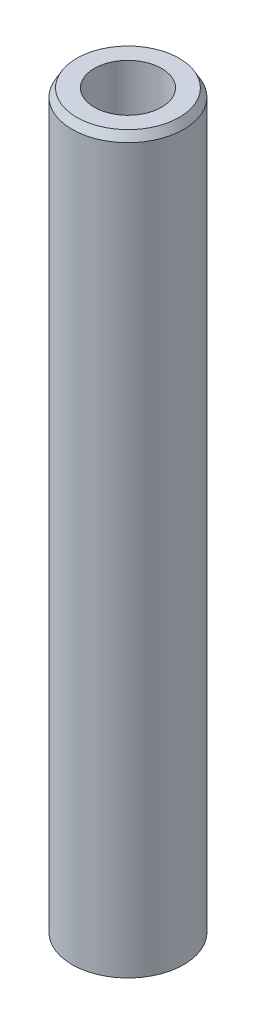
SolidWorks part; units mm, degrees
ref_plane "Front Plane" through (0, 0, 0) normal (0, 0, 1) x (1, 0, 0)
ref_plane "Top Plane" through (0, 0, 0) normal (0, 1, 0) x (1, 0, 0)
ref_plane "Right Plane" through (0, 0, 0) normal (1, 0, 0) x (0, 0, -1)
sketch "Sketch1" plane through (0, 0, 0) normal (0, 1, 0) x (1, 0, 0)
  circle A0 centre (0, 0) radius 30
  dimension "SHAFT_OD" = 60
extrude "Boss-Extrude1" add sketch "Sketch1" along normal blind 395.2318
sketch "Sketch2" plane through (0, 0, 0) normal (0, 1, 0) x (1, 0, 0)
  circle A0 centre (0, 0) radius 18.0728
  dimension "BORE_D" = 36.1455
extrude "Cut-Extrude1" cut sketch "Sketch2" along normal through all
chamfer "Chamfer1" distance 4.3151 angle 30 2 edges at (0, 395.2318, 30) (0, 0, 30) first distance on face at (0, 395.2318, 30) first distance on face at (0, 0, 18.0728)
